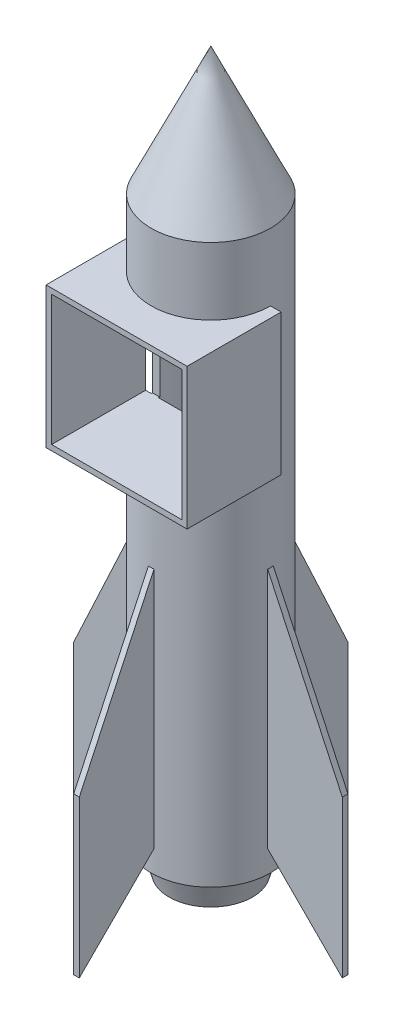
SolidWorks part; units mm, degrees
ref_plane "Front Plane" through (0, 0, 0) normal (0, 0, 1) x (1, 0, 0)
ref_plane "Top Plane" through (0, 0, 0) normal (0, 1, 0) x (1, 0, 0)
ref_plane "Right Plane" through (0, 0, 0) normal (1, 0, 0) x (0, 0, -1)
sketch "Sketch1" plane through (0, 0, 0) normal (0, 0, 1) x (1, 0, 0)
  line L6 (0, 0) -> (0, 152.4)
  line L7 (0, 152.4) -> (12.7, 125.1648)
  line L8 (12.7, 125.1648) -> (12.7, 6.35)
  line L9 (12.7, 6.35) -> (10.8024, 6.35)
  line L10 (10.8024, 6.35) -> (8.89, 0)
  line L11 (8.89, 0) -> (0, 0)
  line L12 (0, -1000) -> (0, 49000) construction
  dimension "D1" = 152.4
  dimension "D2" = 25
  dimension "D3" = 12.7
  dimension "D4" = 8.89
  dimension "D5" = 6.35
  dimension "D6" = 6.6317
revolve "Revolve2" add sketch "Sketch1" angle 360 about L12
sketch "Sketch3" plane through (0, 0, 0) normal (0, 0, 1) x (1, 0, 0)
  line L0 (11.1125, 66.0235) -> (28.575, 28.575)
  line L1 (12.7, 6.35) -> (12.7, 125.1648) construction
  line L2 (28.575, 28.575) -> (28.575, -4.7625)
  line L3 (28.575, -4.7625) -> (11.1125, 12.7)
  line L4 (11.1125, 12.7) -> (11.1125, 66.0235)
  line L5 (-8.89, 0) -> (8.89, 0) construction
  dimension "D1" = 25
  dimension "D2" = 45
  dimension "D3" = 15.875
  dimension "D4" = 4.7625
  dimension "D5" = 33.3375
  dimension "D6" = 1.5875
extrude "Boss-Extrude1" add sketch "Sketch3" along normal mid plane 1.1906
ref_axis "Axis1" through (0, -12.6206, 0) along (0, 1, 0)
pattern_circular "CirPattern1" count 4 over 360 about axis through (0, -12.6206, 0) along (0, 1, 0) of "Boss-Extrude1"
sketch "Sketch5" plane through (0, 0, 0) normal (0, 0, 1) x (1, 0, 0)
  line L0 (0, 0) -> (0, 95.25)
  line L1 (0, -12.6206) -> (0, 160.2581) construction
  line L2 (0, 95.25) -> (11.1125, 95.25)
  line L3 (11.1125, 95.25) -> (11.1125, 10.1322)
  line L4 (11.1125, 10.1322) -> (8.061, 0)
  line L5 (-8.89, 0) -> (8.89, 0) construction
  line L6 (8.061, 0) -> (0, 0)
  line L7 (8.89, 0) -> (10.8024, 6.35) construction
  line L8 (0, -1000) -> (0, 49000) construction
  dimension "D1" = 95.25
  dimension "D2" = 0.7937
  dimension "D3" = 11.1125
revolve "Cut-Revolve1" cut sketch "Sketch5" angle 360 about L8 region at (5.489, 48.2808, 0)
sketch "Sketch6" plane through (-5.9019, 3.8072, 0) normal (0, 0, 1) x (1, 0, 0)
  line L1 (-9.147, 107.0477) -> (20.853, 107.0477)
  line L2 (-9.147, 107.0477) -> (-9.147, 77.0477)
  line L3 (-9.147, 77.0477) -> (20.853, 77.0477)
  line L4 (20.853, 107.0477) -> (20.853, 77.0477)
  dimension "D1" = 30
  dimension "D2" = 30
extrude "Boss-Extrude2" add sketch "Sketch6" along normal blind 20 contours L2 L1 L4 L3
sketch "Sketch8" plane through (72.4429, -2.5799, 0) normal (0, 0, 1) x (1, 0, 0)
  line L1 (-86.3104, 112.3075) -> (-58.6104, 112.3075)
  line L2 (-86.3104, 112.3075) -> (-86.3104, 84.6075)
  line L3 (-86.3104, 84.6075) -> (-58.6104, 84.6075)
  line L4 (-58.6104, 112.3075) -> (-58.6104, 84.6075)
  dimension "D1" = 27.7
  dimension "D2" = 27.7
extrude "Cut-Extrude2" cut sketch "Sketch8" along normal blind 25.636 and the other way blind 0.254
